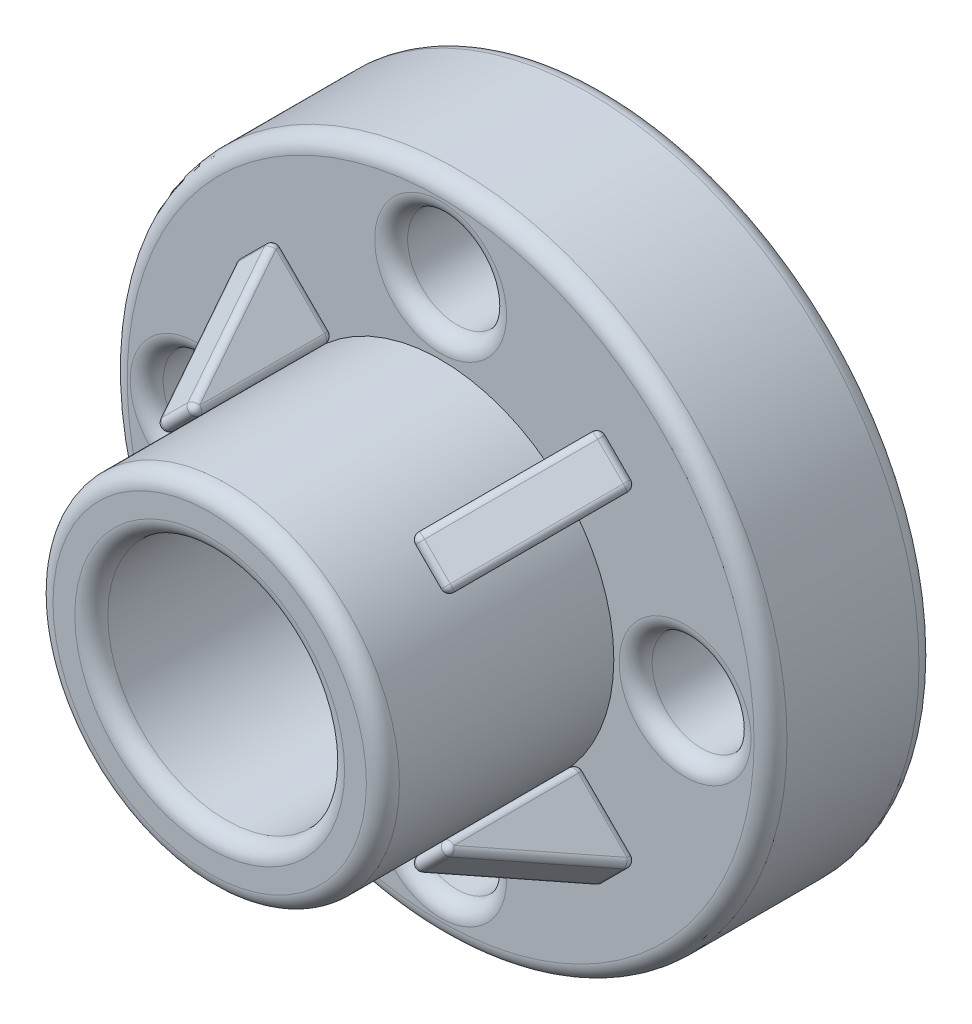
SolidWorks part; units mm, degrees
ref_plane "Front Plane" through (0, 0, 0) normal (0, 0, 1) x (1, 0, 0)
ref_plane "Top Plane" through (0, 0, 0) normal (0, 1, 0) x (1, 0, 0)
ref_plane "Right Plane" through (0, 0, 0) normal (1, 0, 0) x (0, 0, -1)
sketch "Sketch1" plane through (0, 0, 0) normal (0, 0, 1) x (1, 0, 0)
  line L0 (-74.1099, 0) -> (0, 0) construction
  line L1 (-74.1099, 0) -> (0, -74.1099) construction
  line L2 (-74.1099, 0) -> (0, 74.1099) construction
  line L3 (0, 74.1099) -> (74.1099, 0) construction
  line L4 (74.1099, 0) -> (0, -74.1099) construction
  circle A0 centre (0, 0) radius 100
  circle A1 centre (-74.1099, 0) radius 15
  circle A2 centre (0, 74.1099) radius 15
  circle A3 centre (74.1099, 0) radius 15
  circle A4 centre (0, -74.1099) radius 15
  point P5 (-37.055, -37.055)
  point P6 (37.055, -37.055)
  point P7 (37.055, 37.055)
  point P14 (0, 0)
  point P15 (-37.055, 37.055)
  dimension "D1" = 200
  dimension "D2" = 30
  dimension "D3" = 4
extrude "Boss-Extrude1" add sketch "Sketch1" along normal blind 50
sketch "Sketch2" plane through (0, 0, 50) normal (0, 0, 1) x (1, 0, 0)
  circle A0 centre (0, 0) radius 52.5
  dimension "D1" = 105
extrude "Boss-Extrude2" add sketch "Sketch2" along normal blind 70 contours A0
sketch "Sketch3" plane through (0, 0, 120) normal (0, 0, 1) x (1, 0, 0)
  circle A0 centre (0, 0) radius 35.8908
extrude "Cut-Extrude1" cut sketch "Sketch3" against normal through all both and the other way through all
sketch "Sketch4" plane through (0, 0, 50) normal (0, 0, 1) x (1, 0, 0)
  line L0 (-74.1099, 0) -> (0, -74.1099) construction
  line L1 (0, -74.1099) -> (74.1099, 0) construction
  line L2 (74.1099, 0) -> (0, 74.1099) construction
  line L3 (0, 74.1099) -> (-74.1099, 0) construction
  point P4 (-37.055, 37.055)
  point P8 (-37.055, -37.055)
  point P9 (37.055, -37.055)
  point P10 (37.055, 37.055)
ref_plane "Plane1" through (0, 0, 0) normal (-0.7071, 0.7071, 0) x (0.7071, 0.7071, 0)
sketch "Sketch5" plane through (0, 0, 0) normal (-0.7071, 0.7071, 0) x (0.7071, 0.7071, 0)
  line L0 (-52.5, -97.5341) -> (-78.6366, -50)
  line L1 (-52.5, -50) -> (-52.5, -120) construction
  line L2 (-52.5, -97.5341) -> (-52.4036, -50)
  line L3 (-52.4036, -50) -> (-78.6366, -50)
extrude "Boss-Extrude3" add sketch "Sketch5" along normal mid plane 15 separate body contours L0 L3 L2
ref_axis "Axis1" through (0, 0, 0) along (0, 0, 1)
pattern_circular "CirPattern1" count 4 over 360 about axis through (0, 0, 0) along (0, 0, 1) of bodies 104
fillet "Fillet1" radius 5 2 edges at (100, 0, 0) (100, 0, 50)
fillet "Fillet2" radius 5 2 edges at (35.8908, 0, 120) (52.5, 0, 120)
fillet "Fillet3" radius 5 6 edges at (35.8908, 0, 0) (89.1099, 0, 0) (89.1099, 0, 50) (15, -74.1099, 50) (-59.1099, 0, 50) (15, 74.1099, 50)
fillet "Fillet4" radius 2 8 edges at (55.6045, 55.6045, 50) (37.1231, 37.1231, 97.5341) (41.0264, 51.633, 50) (41.0605, 51.6671, 73.7671) (31.7857, 42.3923, 73.7671) (51.6671, 41.0605, 73.7671) (51.633, 41.0264, 50) (42.3923, 31.7857, 73.7671)
fillet "Fillet5" radius 2 9 edges at (55.6045, -55.6045, 50) (41.0605, -51.6671, 73.7671) (37.1231, -37.1231, 97.5341) (51.6671, -41.0605, 73.7671) (37.055, -37.055, 50) (41.0264, -51.633, 50) (31.7857, -42.3923, 73.7671) (51.633, -41.0264, 50) (42.3923, -31.7857, 73.7671)
fillet "Fillet6" radius 2 9 edges at (-55.6045, -55.6045, 50) (-51.6671, -41.0605, 73.7671) (-37.1231, -37.1231, 97.5341) (-41.0605, -51.6671, 73.7671) (-37.055, -37.055, 50) (-51.633, -41.0264, 50) (-42.3923, -31.7857, 73.7671) (-41.0264, -51.633, 50) (-31.7857, -42.3923, 73.7671)
fillet "Fillet7" radius 2 9 edges at (-55.6045, 55.6045, 50) (-41.0605, 51.6671, 73.7671) (-37.1231, 37.1231, 97.5341) (-51.6671, 41.0605, 73.7671) (-37.055, 37.055, 50) (-41.0264, 51.633, 50) (-31.7857, 42.3923, 73.7671) (-51.633, 41.0264, 50) (-42.3923, 31.7857, 73.7671)
